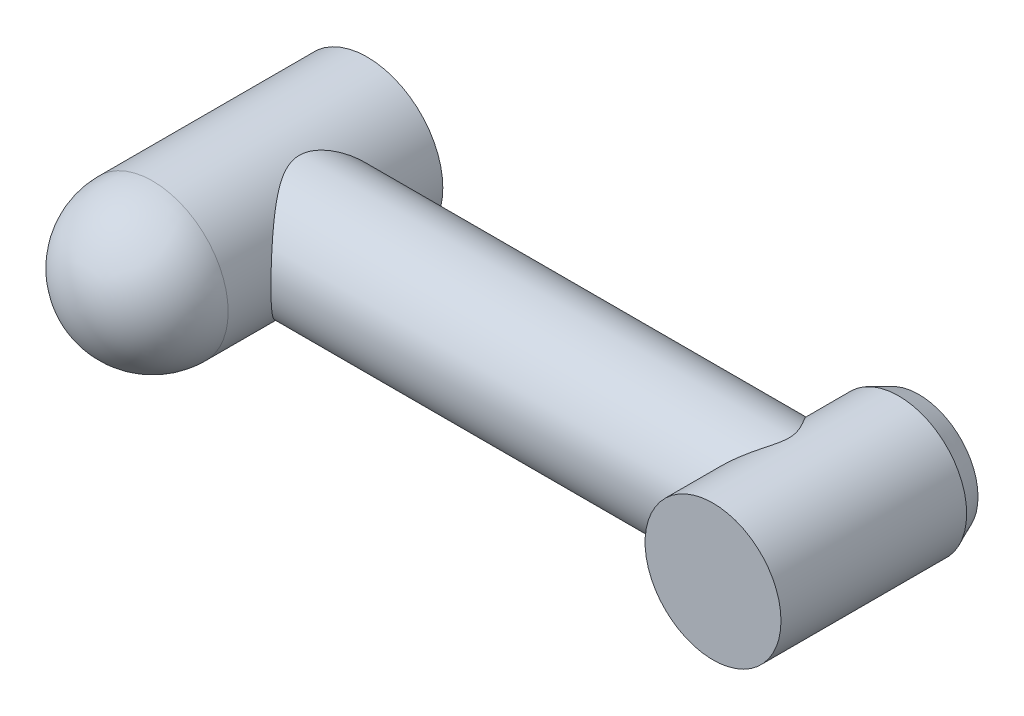
SolidWorks part; units mm, degrees
ref_plane "Front Plane" through (0, 0, 0) normal (0, 0, 1) x (1, 0, 0)
ref_plane "Top Plane" through (0, 0, 0) normal (0, 1, 0) x (1, 0, 0)
ref_plane "Right Plane" through (0, 0, 0) normal (1, 0, 0) x (0, 0, -1)
sketch "Sketch1" plane through (0, 0, 0) normal (0, 0, 1) x (1, 0, 0)
  circle A0 centre (0, 0) radius 60
  dimension "D1" = 120
extrude "Boss-Extrude1" add sketch "Sketch1" along normal blind 230.5
fillet "Fillet1" radius 60 1 edges at (60, 0, 230.5)
sketch "Sketch2" plane through (0, 0, 0) normal (1, 0, 0) x (0, 0, -1)
  line L0 (0, -60) -> (0, 60) construction
  circle A0 centre (-85.5, 0) radius 51
  dimension "D2" = 102
  dimension "D1" = 85.5
extrude "Boss-Extrude2" add sketch "Sketch2" along normal blind 438.15
ref_axis "Axis1" through (438.15, 0, 85.5) along (-1, 0, 0)
ref_plane "Plane1" through (0, 0, 85.5) normal (0, 0, 1) x (1, 0, 0)
sketch "Sketch3" plane through (0, 0, 85.5) normal (0, 0, 1) x (1, 0, 0)
  line L0 (438.15, -51) -> (438.15, 51) construction
  line L1 (438.15, -51) -> (438.15, 51)
  circle A0 centre (438.15, 0) radius 53.975
  dimension "D1" = 107.95
extrude "Boss-Extrude3" add sketch "Sketch3" along normal blind 78 and the other way blind 85.5 contours A0 region at (385.7016, 0, 85.5)
chamfer "Chamfer1" distance 7 distance2 16 1 edges at (492.125, 0, 0) first distance on face at (492.125, 0, 0)
